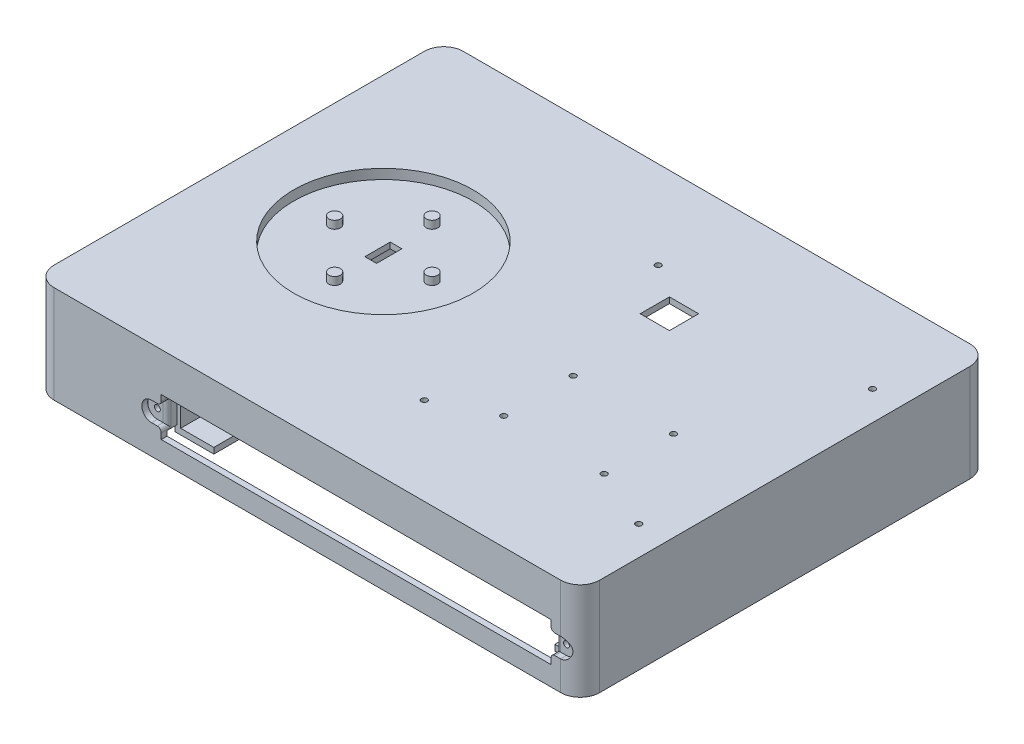
SolidWorks part; units mm, degrees
ref_plane "Front Plane" through (0, 0, 0) normal (0, 0, 1) x (1, 0, 0)
ref_plane "Top Plane" through (0, 0, 0) normal (0, 1, 0) x (1, 0, 0)
ref_plane "Right Plane" through (0, 0, 0) normal (1, 0, 0) x (0, 0, -1)
sketch "Sketch1" plane through (0, 0, 0) normal (0, 1, 0) x (1, 0, 0)
  line L1 (130, -105) -> (-130, -105)
  line L2 (140, -95) -> (140, 95)
  line L3 (130, 105) -> (-130, 105)
  line L4 (-140, -95) -> (-140, 95)
  line L5 (140, -105) -> (-140, 105) construction
  line L6 (140, 105) -> (-140, -105) construction
  arc A0 (-130, -105) -> (-140, -95) centre (-130, -95) cw
  arc A1 (130, -105) -> (140, -95) centre (130, -95) ccw
  arc A2 (140, 95) -> (130, 105) centre (130, 95) ccw
  arc A3 (-130, 105) -> (-140, 95) centre (-130, 95) ccw
  point P0 (0, 0)
  dimension "D3" = 10
  dimension "D1" = 280
  dimension "D2" = 210
extrude "Boss-Extrude1" add sketch "Sketch1" along normal blind 50
sketch "Sketch2" plane through (0, 50, 0) normal (0, 1, 0) x (1, 0, 0)
  circle A0 centre (-66, 0) radius 46
  dimension "D1" = 92
extrude "Cut-Extrude1" cut sketch "Sketch2" against normal blind 5
shell "Shell1" thickness 3 removed face at (0, 0, 0)
sketch "Sketch3" plane through (0, 45, 0) normal (0, 1, 0) x (1, 0, 0)
  line L1 (-63, -6.5) -> (-69, -6.5)
  line L2 (-63, -6.5) -> (-63, 6.5)
  line L3 (-63, 6.5) -> (-69, 6.5)
  line L4 (-69, -6.5) -> (-69, 6.5)
  line L5 (-63, -6.5) -> (-69, 6.5) construction
  line L6 (-63, 6.5) -> (-69, -6.5) construction
  point P0 (-66, 0)
  dimension "D1" = 6
  dimension "D2" = 13
extrude "Cut-Extrude2" cut sketch "Sketch3" against normal blind 10
sketch "Sketch5" plane through (0, 50, 0) normal (0, 1, 0) x (1, 0, 0)
  line L0 (32, 48.7721) -> (47, 48.7721)
  line L1 (47, 48.7721) -> (47, 33.7721)
  line L2 (47, 33.7721) -> (32, 33.7721)
  line L3 (32, 33.7721) -> (32, 48.7721)
  dimension "D1" = 15
extrude "Cut-Extrude3" cut sketch "Sketch5" against normal through all
sketch "Sketch6" plane through (0, 0, 105) normal (0, 0, 1) x (1, 0, 0)
  line L0 (130, 50) -> (130, 0) construction
  line L1 (125, 10) -> (-75, 10)
  line L2 (125, 10) -> (125, 30)
  line L3 (125, 30) -> (-75, 30)
  line L4 (-75, 10) -> (-75, 30)
  line L5 (125, 10) -> (-75, 30) construction
  line L6 (125, 30) -> (-75, 10) construction
  line L7 (-130, 0) -> (130, 0) construction
  point P0 (25, 20)
  dimension "D1" = 20
  dimension "D2" = 200
  dimension "D3" = 5
  dimension "D4" = 10
extrude "Cut-Extrude4" cut sketch "Sketch6" against normal blind 81
sketch "Sketch7" plane through (137, 0, 0) normal (-1, 0, 0) x (0, 0, 1)
  line L0 (102, 10) -> (105, 10) construction
  line L1 (95, 7) -> (-95, 7)
  line L2 (95, 7) -> (95, 10)
  line L3 (95, 10) -> (-95, 10)
  line L4 (-95, 7) -> (-95, 10)
  line L5 (95, 7) -> (-95, 10) construction
  line L6 (95, 10) -> (-95, 7) construction
  line L7 (95, 47) -> (95, 0) construction
  point P0 (0, 8.5)
  dimension "D1" = 3
  dimension "D2" = 0
  dimension "D3" = 0
  dimension "D4" = 190
extrude "Boss-Extrude2" add sketch "Sketch7" along normal blind 20
sketch "Sketch8" plane through (0, 47, 0) normal (0, -1, 0) x (1, 0, 0)
  line L0 (117, 95) -> (137, 95) construction
  line L1 (-75, -95) -> (-78, -95)
  line L2 (-75, -95) -> (-75, 95)
  line L3 (-75, 95) -> (-78, 95)
  line L4 (-78, -95) -> (-78, 95)
  line L5 (-75, -95) -> (-78, 95) construction
  line L6 (-75, 95) -> (-78, -95) construction
  line L7 (-75, 102) -> (-75, 105) construction
  point P0 (-76.5, 0)
  dimension "D1" = 3
  dimension "D2" = 190
  dimension "D3" = 0
  dimension "D4" = 0
extrude "Boss-Extrude3" add sketch "Sketch8" along normal up to surface (40 mm away) up to face at (127, 7, 0)
sketch "Sketch9" plane through (0, 7, 0) normal (0, -1, 0) x (1, 0, 0)
  line L1 (-58, -95) -> (-78, -95)
  line L2 (-58, -95) -> (-58, 95)
  line L3 (-58, 95) -> (-78, 95)
  line L4 (-78, -95) -> (-78, 95)
  line L5 (-58, -95) -> (-78, 95) construction
  line L6 (-58, 95) -> (-78, -95) construction
  point P0 (-68, 0)
  dimension "D1" = 20
  dimension "D2" = 190
extrude "Boss-Extrude4" add sketch "Sketch9" against normal up to surface (3 mm away) up to face at (127, 10, 0)
sketch "Sketch10" plane through (0, 47, 0) normal (0, 1, 0) x (1, 0, 0)
  circle A0 centre (-66, 0) radius 46
extrude "Cut-Extrude5" cut sketch "Sketch10" against normal up to surface (2 mm away) up to face at (-66, 45, 0)
sketch "Sketch11" plane through (0, 50, 0) normal (0, 1, 0) x (1, 0, 0)
  circle A0 centre (42.4006, -11.0255) radius 1.5
  circle A1 centre (93.9006, -11.0255) radius 1.5
  circle A2 centre (93.9006, -46.6255) radius 1.5
  circle A3 centre (42.4006, -46.6255) radius 1.5
extrude "Cut-Extrude6" cut sketch "Sketch11" against normal through all
sketch "Sketch12" plane through (0, 50, 0) normal (0, 1, 0) x (1, 0, 0)
  circle A0 centre (15, 60) radius 1.5
  circle A1 centre (125, 60) radius 1.5
  circle A2 centre (125, -60) radius 1.5
  circle A3 centre (15, -60) radius 1.5
extrude "Cut-Extrude7" cut sketch "Sketch12" against normal blind 3
sketch "Sketch14" plane through (0, 45, 0) normal (0, 1, 0) x (1, 0, 0)
  line L0 (-66, 0) -> (-66, 25) construction
  circle A0 centre (-66, 25) radius 2.95
  circle A1 centre (-66, 0) radius 25 construction
  circle A2 centre (-41, 0) radius 2.95
  circle A3 centre (-66, -25) radius 2.95
  circle A4 centre (-91, 0) radius 2.95
  dimension "D1" = 5.9
  dimension "D2" = 50
  dimension "D3" = 4
extrude "Boss-Extrude5" add sketch "Sketch14" along normal blind 4
fillet "Fillet1" radius 2 6 edges at (-78, 44.5, -47.5079) (-78, 44.5, 47.5079) (-78, 47, 71.2539) (-78, 42, 0) (-78, 47, -71.2539) (137, 7, 0)
sketch "Sketch15" plane through (0, 0, 105) normal (0, 0, 1) x (1, 0, 0)
  line L3 (-76.95, 25) -> (-79.95, 25)
  line L4 (-76.95, 15) -> (-76.95, 25)
  line L5 (-79.95, 15) -> (-76.95, 15)
  line L6 (-76.95, 25) -> (-79.95, 25)
  line L8 (-79.95, 15) -> (-76.95, 15)
  line L9 (126.95, 15) -> (129.95, 15)
  line L10 (126.95, 25) -> (126.95, 15)
  line L11 (129.95, 25) -> (126.95, 25)
  line L12 (126.95, 15) -> (129.95, 15)
  line L14 (129.95, 25) -> (126.95, 25)
  line L27 (-76.95, 25) -> (-75, 25)
  line L28 (-75, 30) -> (-75, 10) construction
  line L29 (-75, 25) -> (-75, 15)
  line L32 (-75, 15) -> (-76.95, 15)
  line L33 (126.95, 25) -> (125, 25)
  line L34 (125, 10) -> (125, 30) construction
  line L35 (125, 25) -> (125, 15)
  line L36 (125, 15) -> (126.95, 15)
  arc A1 (-79.95, 25) -> (-79.95, 15) centre (-79.95, 20) ccw
  arc A2 (-79.95, 25) -> (-79.95, 15) centre (-79.95, 20) ccw
  arc A3 (129.95, 15) -> (129.95, 25) centre (129.95, 20) ccw
  arc A4 (129.95, 15) -> (129.95, 25) centre (129.95, 20) ccw
  dimension "D1" = 0
  dimension "D2" = 0
extrude "Cut-Extrude8" cut sketch "Sketch15" against normal blind 3
sketch "Sketch17" plane through (0, 0, 102) normal (0, 0, -1) x (-1, 0, 0)
  line L0 (75, 10) -> (75, 47) construction
  line L1 (84.9, 12.5) -> (75, 12.5)
  line L2 (84.9, 12.5) -> (84.9, 27.5)
  line L3 (84.9, 27.5) -> (75, 27.5)
  line L4 (75, 12.5) -> (75, 27.5)
  line L5 (84.9, 12.5) -> (75, 27.5) construction
  line L6 (84.9, 27.5) -> (75, 12.5) construction
  line L7 (-130, 24.9997) -> (-130, 15.0003) construction
  line L8 (-135, 12.5) -> (-125, 12.5)
  line L9 (-135, 12.5) -> (-135, 27.5)
  line L10 (-135, 27.5) -> (-125, 27.5)
  line L11 (-125, 12.5) -> (-125, 27.5)
  line L12 (-135, 12.5) -> (-125, 27.5) construction
  line L13 (-135, 27.5) -> (-125, 12.5) construction
  line L14 (-125, 30) -> (-125, 25) construction
  point P0 (79.95, 20)
  point P8 (-130, 20)
  dimension "D1" = 15
  dimension "D2" = 15
extrude "Boss-Extrude6" add sketch "Sketch17" along normal blind 5
sketch "Sketch18" plane through (0, 0, 105) normal (0, 0, 1) x (1, 0, 0)
  circle A0 centre (-79.95, 20) radius 1.5
  circle A1 centre (129.95, 20) radius 1.5
extrude "Cut-Extrude9" cut sketch "Sketch18" against normal blind 8
fillet "Fillet2" radius 2 6 edges at (125, 25, 103.5) (125, 20, 102) (125, 15, 103.5) (-75, 20, 102) (-75, 15, 103.5) (-75, 25, 103.5)
